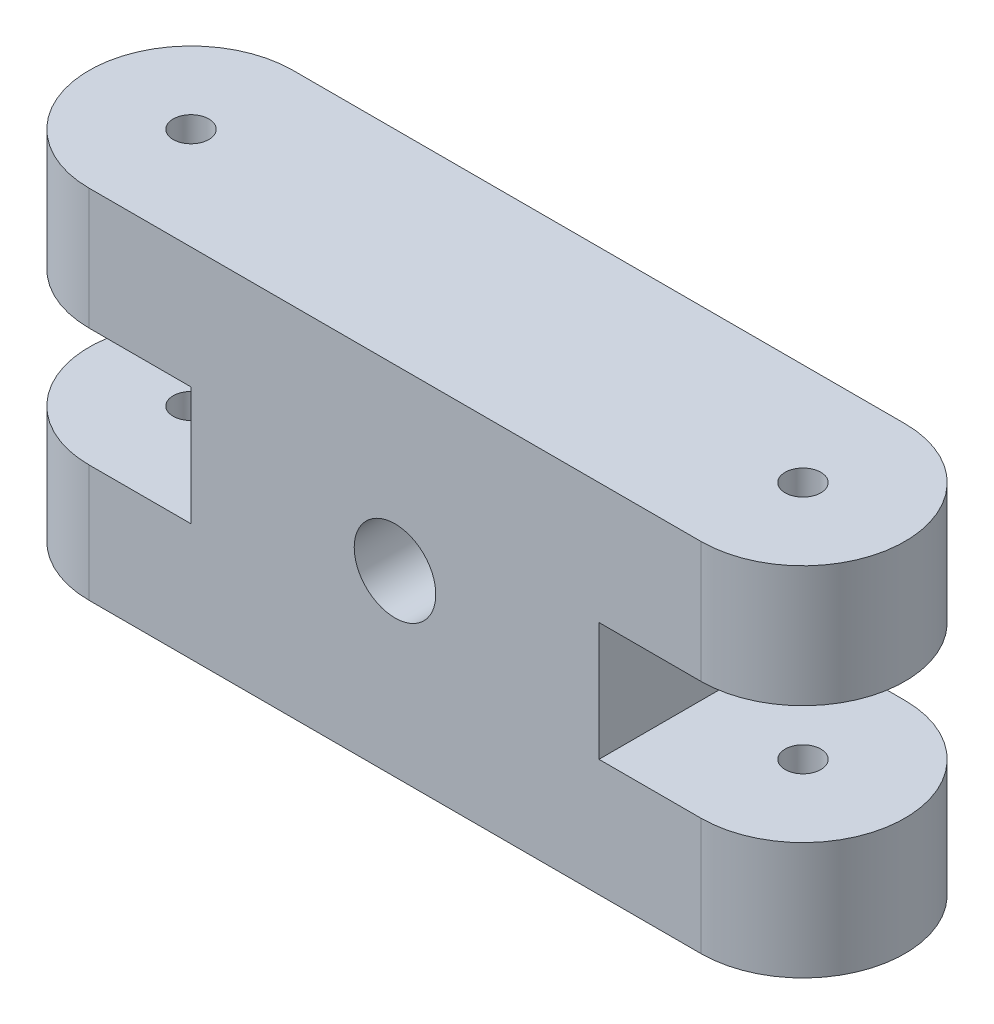
SolidWorks part; units mm, degrees
ref_plane "Front Plane" through (0, 0, 0) normal (0, 0, 1) x (1, 0, 0)
ref_plane "Top Plane" through (0, 0, 0) normal (0, 1, 0) x (1, 0, 0)
ref_plane "Right Plane" through (0, 0, 0) normal (1, 0, 0) x (0, 0, -1)
sketch "Sketch1" plane through (0, 0, 0) normal (0, 1, 0) x (1, 0, 0)
  line L1 (-30, -10) -> (30, -10)
  line L2 (-30, -10) -> (-30, 10)
  line L3 (-30, 10) -> (30, 10)
  line L4 (30, -10) -> (30, 10)
  line L5 (-30, -10) -> (30, 10) construction
  line L6 (-30, 10) -> (30, -10) construction
  circle A0 centre (-30, 0) radius 10
  circle A1 centre (30, 0) radius 10
  circle A2 centre (-30, 0) radius 1.75
  circle A3 centre (30, 0) radius 1.75
  point P0 (0, 0)
extrude "Boss-Extrude1" add sketch "Sketch1" along normal blind 35 contours A3 L4 A1 | A2 L2 A0 | A1 L3 A0 L1 | A2 L2 A0 | A3 L4 A1 region at (0, 0, 0) region at (-34.3548, 0, 0) region at (-25.6452, 0, 0) region at (25.6452, 0, 0) region at (34.3548, 0, 0)
sketch "Sketch3" plane through (0, 0, -10) normal (0, 0, -1) x (-1, 0, 0)
  line L0 (30, 17.5) -> (30, 23.1186)
  line L1 (30, 35) -> (-30, 35)
  line L2 (30, 35) -> (30, 0)
  line L3 (30, 0) -> (-30, 0)
  line L4 (-30, 35) -> (-30, 0)
  line L5 (30, 17.5) -> (30, 11.5)
  line L6 (30, 11.5) -> (20, 11.5)
  line L7 (20, 11.5) -> (20, 23.1186)
  line L8 (20, 23.1186) -> (44.5181, 23.1186)
  line L9 (44.5181, 23.1186) -> (44.5181, 11.5)
  line L10 (44.5181, 11.5) -> (30, 11.5)
  line L11 (0, 17.5) -> (0, 9.7831)
  line L12 (-44.5181, 11.5) -> (-30, 11.5)
  line L13 (-44.5181, 23.1186) -> (-44.5181, 11.5)
  line L14 (-20, 23.1186) -> (-44.5181, 23.1186)
  line L15 (-20, 11.5) -> (-20, 23.1186)
  line L16 (-30, 11.5) -> (-20, 11.5)
  line L17 (-30, 17.5) -> (-30, 11.5)
  line L18 (-30, 17.5) -> (-30, 23.1186)
  circle A0 centre (0, 17.5) radius 4
  line M13 (30, 0) -> (30, 35)
  line M15 (-30, 35) -> (-30, 0)
extrude "Cut-Extrude1" cut sketch "Sketch3" against normal blind 20 contours A0 | L8 L7 L6 L2 M13 | L10 L9 L8 L2 M13 | L4 L16 L15 L14 M15 | L4 L14 L13 L12 M15 region at (-25, 17.3093, -10) region at (-37.2591, 17.3093, -10) region at (25, 17.3093, -10) region at (37.2591, 17.3093, -10) region at (-2.7484, 14.7516, -10)
